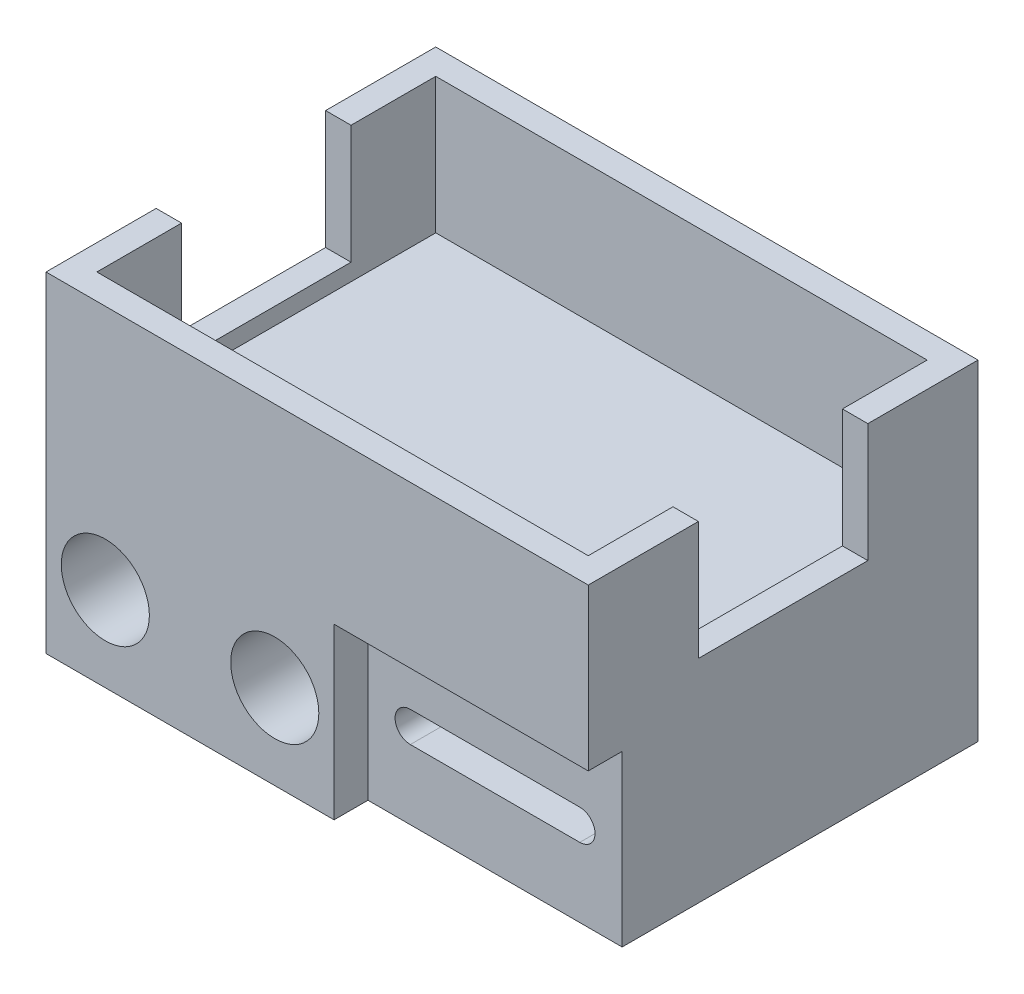
SolidWorks part; units mm, degrees
ref_plane "Front Plane" through (0, 0, 0) normal (0, 0, 1) x (1, 0, 0)
ref_plane "Top Plane" through (0, 0, 0) normal (0, 1, 0) x (1, 0, 0)
ref_plane "Right Plane" through (0, 0, 0) normal (1, 0, 0) x (0, 0, -1)
sketch "Sketch4" plane through (0, 0, 0) normal (0, 1, 0) x (1, 0, 0)
  line L1 (-16, -11.5) -> (16, -11.5)
  line L2 (-16, -11.5) -> (-16, 11.5)
  line L3 (-16, 11.5) -> (16, 11.5)
  line L4 (16, -11.5) -> (16, 11.5)
  line L5 (-16, -11.5) -> (16, 11.5) construction
  line L6 (-16, 11.5) -> (16, -11.5) construction
  point P0 (0, 0)
  dimension "D1" = 32
  dimension "D2" = 23
extrude "Boss-Extrude3" add sketch "Sketch4" along normal blind 9.5
sketch "Sketch5" plane through (0, 9.5, 0) normal (0, 1, 0) x (1, 0, 0)
  line L1 (-14.5, -10) -> (14.5, -10)
  line L2 (-14.5, -10) -> (-14.5, 10)
  line L3 (-14.5, 10) -> (14.5, 10)
  line L4 (14.5, -10) -> (14.5, 10)
  line L5 (-14.5, -10) -> (14.5, 10) construction
  line L6 (-14.5, 10) -> (14.5, -10) construction
  point P0 (0, 0)
  dimension "D1" = 29
  dimension "D2" = 20
extrude "Cut-Extrude2" cut sketch "Sketch5" against normal blind 8
sketch "Sketch7" plane through (16, 0, 0) normal (1, 0, 0) x (0, 0, -1)
  line L1 (-5, 2.5) -> (5, 2.5)
  line L2 (-5, 2.5) -> (-5, 9.5)
  line L3 (-5, 9.5) -> (5, 9.5)
  line L4 (5, 2.5) -> (5, 9.5)
  line L5 (-11.5, 9.5) -> (11.5, 9.5) construction
  point P6 (0, 9.5)
  point P8 (0, 9.5)
  dimension "D1" = 10
  dimension "D2" = 7
extrude "Cut-Extrude4" cut sketch "Sketch7" against normal through all
sketch "Sketch8" plane through (0, 0, 0) normal (0, -1, 0) x (-1, 0, 0)
  line L0 (-16, -9.5) -> (-1, -9.5)
  line L1 (-16, -11.5) -> (-16, 11.5) construction
  line L2 (-1, -9.5) -> (-1, -11.5)
  line L3 (16, -11.5) -> (-16, -11.5) construction
  line L4 (-1, -11.5) -> (16, -11.5)
  line L5 (16, -11.5) -> (16, 9.5)
  line L6 (16, 11.5) -> (16, -11.5) construction
  line L7 (16, 9.5) -> (1, 9.5)
  line L8 (1, 9.5) -> (1, 11.5)
  line L9 (-16, 11.5) -> (16, 11.5) construction
  line L10 (1, 11.5) -> (-16, 11.5)
  line L11 (-16, 11.5) -> (-16, -9.5)
  dimension "D1" = 2
  dimension "D2" = 15
extrude "Boss-Extrude4" add sketch "Sketch8" along normal blind 10
sketch "Sketch9" plane through (0, 0, -9.5) normal (0, 0, -1) x (-1, 0, 0)
  line L0 (3.5, -5) -> (13.5, -5) construction
  line L1 (3.5, -4.1) -> (13.5, -4.1)
  line L2 (3.5, -5.9) -> (13.5, -5.9)
  line L3 (16, -10) -> (1, -10) construction
  line L4 (16, -10) -> (16, 0) construction
  arc A0 (3.5, -4.1) -> (3.5, -5.9) centre (3.5, -5) ccw
  arc A1 (13.5, -5.9) -> (13.5, -4.1) centre (13.5, -5) ccw
  point P2 (8.5, -5)
  point P10 (8.5, -10)
  point P15 (16, -5)
  dimension "D1" = 1.8
  dimension "D2" = 10
ref_plane "Plane1" through (0, 0, 0) normal (0, 0, -1) x (-1, 0, 0)
extrude "Cut-Extrude5" cut sketch "Sketch9" against normal blind 5
sketch "Sketch10" plane through (0, -10, 0) normal (0, -1, 0) x (-1, 0, 0)
  line L0 (-16, 11.5) -> (-16, -9.5) construction
  line L1 (-1, -5.5) -> (-15, -5.5)
  line L2 (-1, -5.5) -> (-1, -2.5)
  line L3 (-1, -2.5) -> (-15, -2.5)
  line L4 (-15, -5.5) -> (-15, -2.5)
  line L5 (-1, -9.5) -> (-1, -11.5) construction
  line L6 (-16, -9.5) -> (-1, -9.5) construction
  line L7 (-5.5, 1) -> (-5.5, 15) [skipped]
  line L8 (-5.5, 1) -> (-2.5, 1) [skipped]
  line L9 (-2.5, 1) -> (-2.5, 15) [skipped]
  line L10 (-5.5, 15) -> (-2.5, 15) [skipped]
  line L11 (1, 5.5) -> (15, 5.5)
  line L12 (1, 5.5) -> (1, 2.5)
  line L13 (1, 2.5) -> (15, 2.5)
  line L14 (15, 5.5) -> (15, 2.5)
  line L15 (5.5, -1) -> (5.5, -15) [skipped]
  line L16 (5.5, -1) -> (2.5, -1) [skipped]
  line L17 (2.5, -1) -> (2.5, -15) [skipped]
  line L18 (5.5, -15) -> (2.5, -15) [skipped]
  line L19 (0, 0) -> (-1, -2.5) construction
  line L20 (10.725, 0) -> (-10.725, 0) construction
  dimension "D1" = 3
  dimension "D2" = 1
  dimension "D3" = 4
  dimension "D4" = 4
extrude "Cut-Extrude6" cut sketch "Sketch10" against normal offset from surface (7.9 mm away) 2 up to face at (-8.5, -4.1, -7) offset beyond the face yes
ref_axis "Axis1" through (0, 0, 0) along (0, -1, 0)
pattern_circular "CirPattern1" count 2 over 360 about axis through (0, 0, 0) along (0, -1, 0) of "Cut-Extrude5"
sketch "Sketch11" plane through (0, 0, -11.5) normal (0, 0, -1) x (-1, 0, 0)
  line L0 (-12.5, -5) -> (-2.5, -5) construction
  line L1 (1, -10) -> (-16, -10) construction
  circle A0 centre (-12.5, -5) radius 2.6
  circle A1 centre (-2.5, -5) radius 2.6
  arc A2 (3.5, -4.1) -> (3.5, -5.9) centre (3.5, -5) ccw construction
  point P6 (-7.5, -10)
  point P10 (2.6, -5)
  point P11 (-7.5, -5)
  dimension "D1" = 5.2
  dimension "D2" = 10
extrude "Cut-Extrude7" cut sketch "Sketch11" against normal blind 7
pattern_circular "CirPattern2" count 2 over 360 about axis through (0, 0, 0) along (0, -1, 0) of "Cut-Extrude7"
sketch "Sketch12" plane through (0, 0, 4.5) normal (0, 0, 1) x (1, 0, 0)
  circle A0 centre (-2.5, -5) radius 1.7
  circle A1 centre (-12.5, -5) radius 1.7
  dimension "D1" = 3.4
extrude "Cut-Extrude8" cut sketch "Sketch12" against normal up to surface (10 mm away) up to face at (-8, -6.05, -5.5)
sketch "Sketch13" plane through (0, 0, -4.5) normal (0, 0, -1) x (-1, 0, 0)
  circle A0 centre (-12.5, -5) radius 1.7
  circle A1 centre (-2.5, -5) radius 1.7
  dimension "D1" = 3.4
extrude "Cut-Extrude9" cut sketch "Sketch13" against normal up to surface (10 mm away) up to face at (8.5, -5, 5.5)
